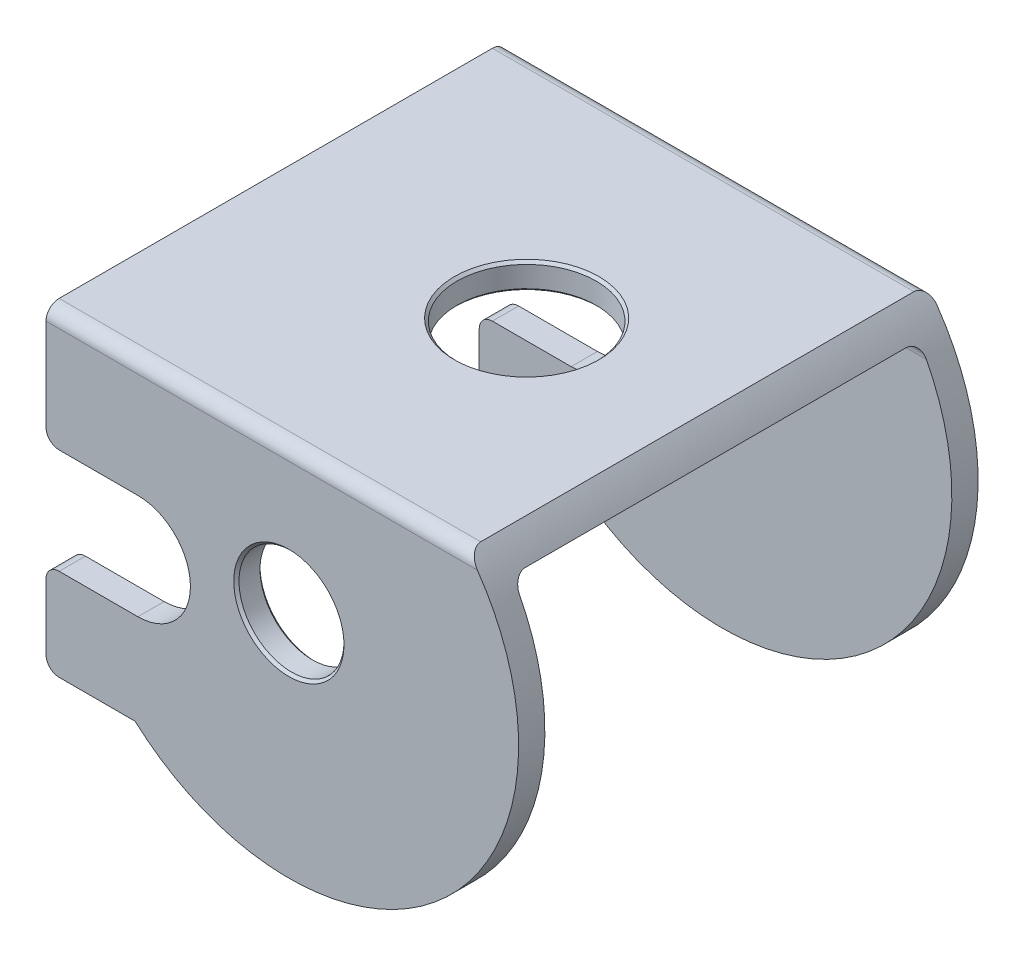
SolidWorks part; units mm, degrees
ref_plane "正面" through (0, 0, 0) normal (0, 0, 1) x (1, 0, 0)
ref_plane "平面" through (0, 0, 0) normal (0, 1, 0) x (1, 0, 0)
ref_plane "右側面" through (0, 0, 0) normal (1, 0, 0) x (0, 0, -1)
sketch "ｽｹｯﾁ1" plane through (0, 0, 0) normal (0, 0, 1) x (1, 0, 0)
  line L0 (-18.5, 11) -> (-18.5, -13)
  line L1 (-18.5, -13) -> (-11.7154, -13)
  line L2 (-18.5, 11) -> (13.6107, 11)
  arc A1 (-11.7154, -13) -> (13.6107, 11) centre (0, 0) ccw
  dimension "D4" = 11
  dimension "D3" = 18.5
  dimension "D2" = 35
  dimension "D1" = 24
extrude "GearB-W" add sketch "ｽｹｯﾁ1" along normal mid plane 35
sketch "ｽｹｯﾁ2" plane through (0, 0, 17.5) normal (0, 0, 1) x (1, 0, 0)
  line L0 (-18.5, 11) -> (-18.5, -13) construction
  line L1 (-18.5, 2) -> (-11.5, 2)
  line L2 (-18.5, 2) -> (-18.5, -6)
  line L3 (-18.5, -6) -> (-11.5, -6)
  line L5 (13.6107, 11) -> (-18.5, 11) construction
  arc A0 (-11.5, -6) -> (-11.5, 2) centre (-11.5, -2) ccw
  circle A1 centre (0, 0) radius 4
  dimension "D6" = 8
  dimension "D1" = 8
  dimension "D2" = 9
  dimension "D5" = 7
extrude "ｶｯﾄ - 押し出し1" cut sketch "ｽｹｯﾁ2" against normal through all
sketch "GearB-t" plane through (-18.5, 0, 0) normal (-1, 0, 0) x (0, 0, 1)
  line L14 (15.5, -17.5) -> (-15.5, -17.5)
  line L17 (-15.5, 9) -> (-15.5, -17.5)
  line L18 (15.5, 9) -> (-15.5, 9)
  line L19 (15.5, -17.5) -> (15.5, 9)
  line L20 (-15.5, 9) -> (-15.5, -17.5)
  line L21 (15.5, 9) -> (-15.5, 9)
  line L22 (15.5, -17.5) -> (15.5, 9)
  dimension "D1" = 2
extrude "ｶｯﾄ - 押し出し2" cut sketch "GearB-t" against normal through all
sketch "ｽｹｯﾁ4" plane through (0, 11, 0) normal (0, 1, 0) x (1, 0, 0)
  line L0 (13.6107, -17.5) -> (13.6107, 17.5) construction
  circle A0 centre (0.6107, 0) radius 5.3
  dimension "D1" = 13
  dimension "D3" = 10.6
extrude "ｶｯﾄ - 押し出し3" cut sketch "ｽｹｯﾁ4" against normal up to next
fillet "ﾌｨﾚｯﾄ1" radius 1 6 edges at (-18.5, -13, -16.5) (-18.5, -13, 16.5) (-18.5, -6, -16.5) (-18.5, -6, 16.5) (-18.5, 2, -16.5) (-18.5, 2, 16.5)
fillet "ﾌｨﾚｯﾄ2" radius 1 4 edges at (-2.4447, 11, -17.5) (-2.4447, 11, 17.5) (-1.7458, 9, -15.5) (-1.7458, 9, 15.5)
chamfer "面取り1" distance 0.2 angle 45 6 edges at (4, 0, 15.5) (4, 0, 17.5) (0, 4, -15.5) (4, 0, -17.5) (-4.6893, 9, 0) (0.6107, 11, 5.3)
